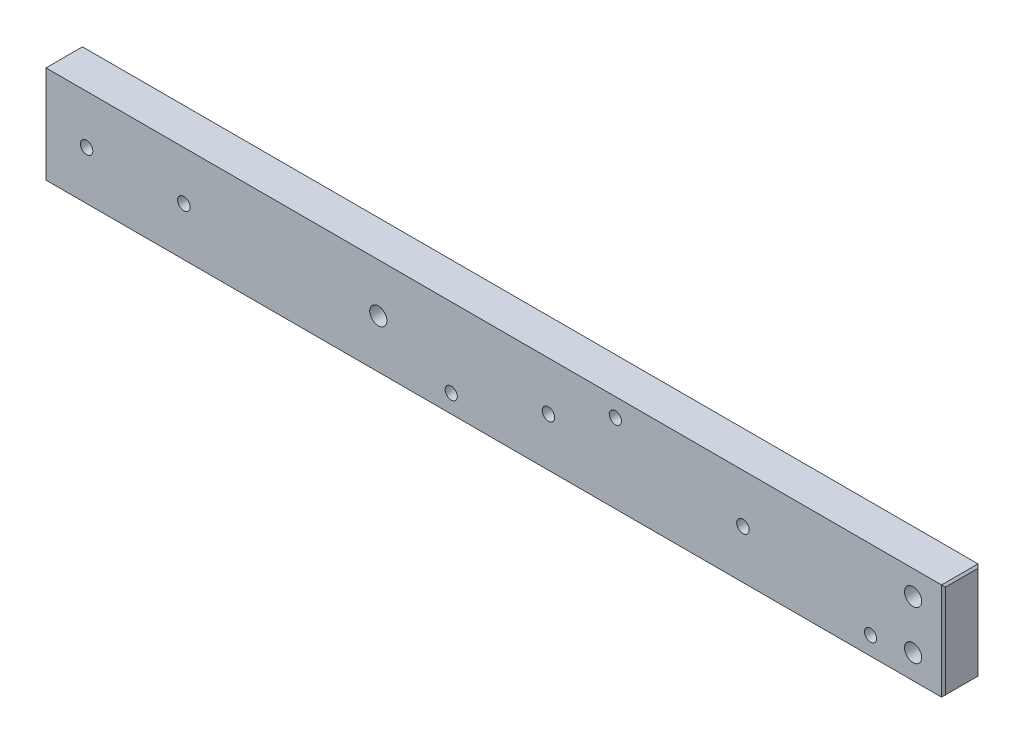
SolidWorks part; units mm, degrees
material "6061-T6 (SS)"
ref_plane "Front Plane" through (0, 0, 0) normal (0, 0, 1) x (1, 0, 0)
ref_plane "Top Plane" through (0, 0, 0) normal (0, 1, 0) x (1, 0, 0)
ref_plane "Right Plane" through (0, 0, 0) normal (1, 0, 0) x (0, 0, -1)
sketch "Sketch1" plane through (0, 0, 0) normal (0, 0, 1) x (1, 0, 0)
  line L1 (0, 0) -> (-234.95, 0)
  line L2 (0, 0) -> (0, 25.4)
  line L3 (0, 25.4) -> (-234.95, 25.4)
  line L4 (-234.95, 0) -> (-234.95, 25.4)
  dimension "D1" = 25.4
  dimension "D2" = 234.95
extrude "Boss-Extrude1" add sketch "Sketch1" along normal blind 9.525
sketch "Sketch2" plane through (0, 0, 9.525) normal (0, 0, 1) x (1, 0, 0)
  line L0 (-7.9375, 6.35) -> (-7.9375, 19.05)
  line L1 (-7.9375, 19.05) -> (-7.9375, 25.4)
  line L2 (0, 25.4) -> (-234.95, 25.4) construction
  line L3 (-7.9375, 6.35) -> (-7.9375, 0)
  line L4 (-234.95, 0) -> (0, 0) construction
  line L5 (0, 0) -> (0, 25.4) construction
  dimension "D1" = 7.9375
  dimension "D2" = 12.7
hole_wizard "#8 Clearance Hole1" positions "Sketch3" profile "Sketch4" hole size "#8" standard "ANSI Inch"
sketch "Sketch3" plane through (0, 0, 9.525) normal (0, 0, 1) x (1, 0, 0)
  point P0 (-7.9375, 6.35)
  point P3 (-7.9375, 19.05)
sketch "Sketch4" plane through (-7.9375, 6.35, 9.525) normal (1, 0, 0) x (0, -1, 0)
  line L0 (0, 0) -> (0, 26.7507)
  line L1 (0, 26.7507) -> (2.2479, 25.4)
  line L2 (2.2479, 25.4) -> (2.2479, 0)
  line L5 (2.2479, 0) -> (0, 0)
  line L10 (0, 26.7507) -> (-2.2479, 25.4) construction
  line L11 (0, -6.35) -> (0, 107.95) construction
  dimension "Hole Dia." = 4.4958
  dimension "Hole Depth" = 25.4
  dimension "Drill Angle" = 118
hole_wizard "#8 Clearance Hole2" positions "Sketch8" profile "Sketch9" hole size "#8" standard "ANSI Inch"
sketch "Sketch8" plane through (0, 0, 9.525) normal (0, 0, 1) x (1, 0, 0)
  line L0 (-211.1375, 12.7) -> (-147.6375, 12.7)
  line L1 (-211.1375, 12.7) -> (-234.95, 12.7)
  line L2 (-234.95, 25.4) -> (-234.95, 0) construction
  point P2 (-147.6375, 12.7)
  dimension "D1" = 63.5
  dimension "D2" = 23.8125
sketch "Sketch9" plane through (-147.6375, 12.7, 9.525) normal (1, 0, 0) x (0, -1, 0)
  line L0 (0, 0) -> (0, 20.4007)
  line L1 (0, 20.4007) -> (2.2479, 19.05)
  line L2 (2.2479, 19.05) -> (2.2479, 0)
  line L5 (2.2479, 0) -> (0, 0)
  line L10 (0, 20.4007) -> (-2.2479, 19.05) construction
  line L11 (0, -6.35) -> (0, 107.95) construction
  dimension "Hole Dia." = 4.4958
  dimension "Hole Depth" = 19.05
  dimension "Drill Angle" = 118
chamfer "Chamfer1" distance 0.508 angle 45 8 edges at (0, 0, 4.7625) (0, 12.7, 9.525) (0, 25.4, 4.7625) (0, 12.7, 0) (-234.95, 25.4, 4.7625) (-234.95, 12.7, 9.525) (-234.95, 0, 4.7625) (-234.95, 12.7, 0)
hole_wizard "#4 Clearance Hole3" positions "Sketch10" profile "Sketch12" hole size "#4" standard "ANSI Inch" end condition through all
sketch "Sketch10" plane through (0, 0, 0) normal (0, 0, -1) x (-1, 0, 0)
  point P0 (103.1875, 12.7)
  point P3 (52.3875, 12.7)
sketch "Sketch12" plane through (-103.1875, 12.7, 0) normal (1, 0, 0) x (0, 1, 0)
  line L0 (0, 0) -> (0, 9.525)
  line L1 (0, 9.525) -> (1.6319, 9.525)
  line L2 (1.6319, 9.525) -> (1.6319, 0)
  line L5 (1.6319, 0) -> (0, 0)
  line L11 (0, -6.35) -> (0, 107.95) construction
  dimension "Thru Hole Dia." = 3.2639
  dimension "Thru Hole Depth" = 9.525
hole_wizard "#4 Clearance Hole2" positions "Sketch13" profile "Sketch14" hole size "#4" standard "ANSI Inch" end condition up to next
sketch "Sketch13" plane through (0, 0, 9.525) normal (0, 0, 1) x (1, 0, 0)
  line L0 (-223.8375, 12.7) -> (-198.4375, 12.7)
  line L2 (-234.442, 25.4) -> (-234.442, 0) construction
  line L3 (-147.6375, 12.7) -> (-211.1375, 12.7) construction
  point P0 (-223.8375, 12.7)
  point P2 (-198.4375, 12.7)
  point P11 (-234.442, 12.7)
  dimension "D1" = 25.4
  dimension "D2" = 63.5
sketch "Sketch14" plane through (-223.8375, 12.7, 9.525) normal (1, 0, 0) x (0, -1, 0)
  line L0 (0, 0) -> (0, 9.525)
  line L1 (0, 9.525) -> (1.6319, 9.525)
  line L2 (1.6319, 9.525) -> (1.6319, 0)
  line L5 (1.6319, 0) -> (0, 0)
  line L11 (0, -6.35) -> (0, 107.95) construction
  dimension "Thru Hole Dia." = 3.2639
  dimension "Thru Hole Depth" = 9.525
hole_wizard "1/8 (0.125) Diameter Hole1" positions "Sketch15" profile "Sketch17" hole size "1/8" standard "ANSI Inch" end condition up to next
sketch "Sketch15" plane through (0, 0, 9.525) normal (0, 0, 1) x (1, 0, 0)
  line L1 (0, 24.892) -> (0, 0.508) construction
  line L2 (-85.725, 20.6375) -> (-19.05, 4.7625)
  line L6 (-234.442, 0) -> (-0.508, 0) construction
  line L7 (-234.442, 0) -> (-0.508, 0) construction
  line L8 (-0.508, 25.4) -> (-234.442, 25.4) construction
  line L9 (-134.9375, 0) -> (-134.9375, 25.4) construction
  point P0 (-19.05, 4.7625)
  point P2 (-85.725, 20.6375)
  point P22 (-128.5875, 4.7625)
  dimension "D1" = 85.725
  dimension "D2" = 19.05
  dimension "D3" = 4.7625
  dimension "D4" = 4.7625
  dimension "D5" = 6.35
  dimension "D6" = 4.7625
sketch "Sketch17" plane through (-19.05, 4.7625, 9.525) normal (1, 0, 0) x (0, -1, 0)
  line L0 (0, 0) -> (0, 9.525)
  line L1 (0, 9.525) -> (1.5875, 9.525)
  line L2 (1.5875, 9.525) -> (1.5875, 0)
  line L5 (1.5875, 0) -> (0, 0)
  line L11 (0, -6.35) -> (0, 107.95) construction
  dimension "Thru Hole Dia." = 3.175
  dimension "Thru Hole Depth" = 9.525
